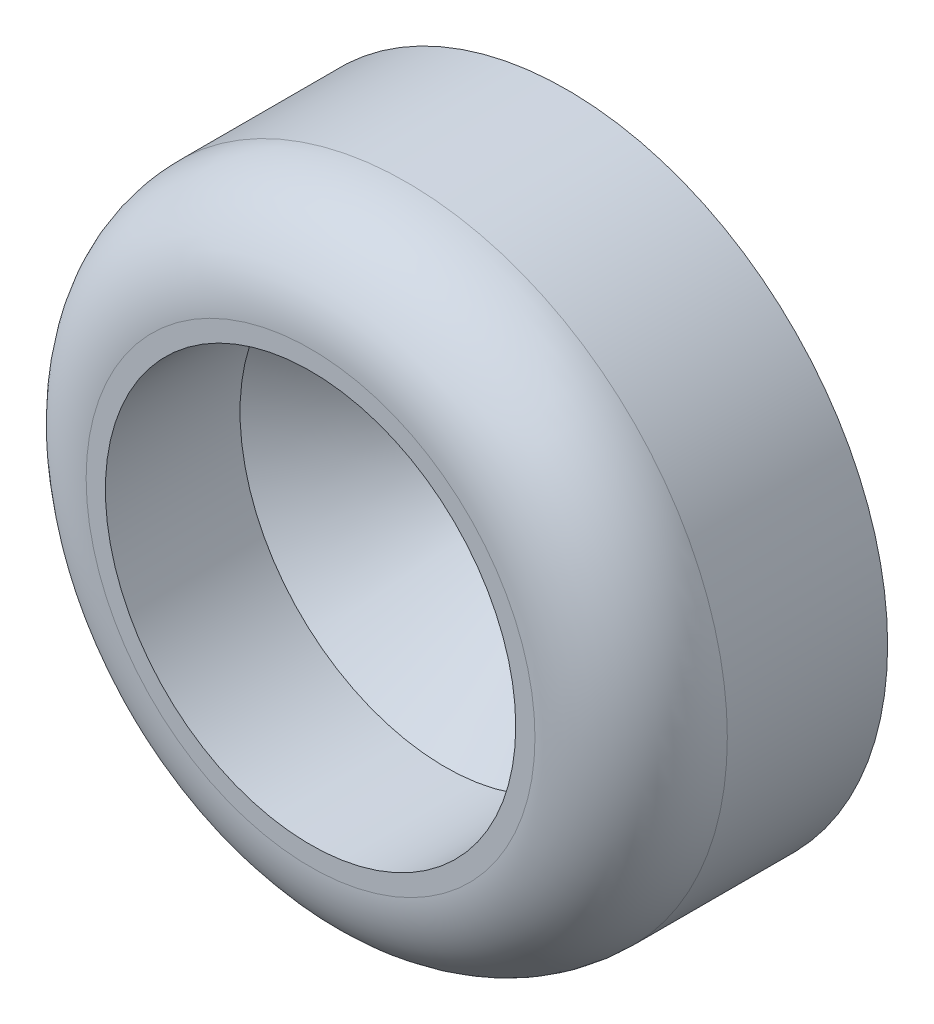
SolidWorks part; units mm, degrees
material "Custom Plastic"
ref_plane "Front Plane" through (0, 0, 0) normal (0, 0, 1) x (1, 0, 0)
ref_plane "Top Plane" through (0, 0, 0) normal (0, 1, 0) x (1, 0, 0)
ref_plane "Right Plane" through (0, 0, 0) normal (1, 0, 0) x (0, 0, -1)
sketch "Sketch1" plane through (0, 0, 0) normal (0, 0, 1) x (1, 0, 0)
  circle A0 centre (0, 0) radius 5
  circle A1 centre (0, 0) radius 1.6
  dimension "D1" = 3.2
  dimension "D2" = 10
extrude "Boss-Extrude1" add sketch "Sketch1" along normal blind 4
sketch "Sketch2" plane through (0, 0, 4) normal (0, 0, 1) x (1, 0, 0)
  circle A0 centre (0, 0) radius 3.2
  dimension "D1" = 6.4
extrude "Cut-Extrude1" cut sketch "Sketch2" against normal offset from surface (1.9 mm away) 2.1 up to face at (5, 0, 0)
chamfer "Chamfer1" distance 1.8 angle 45 1 edges at (1.6, 0, 2.1)
fillet "Fillet1" radius 1.5 1 edges at (5, 0, 4)
